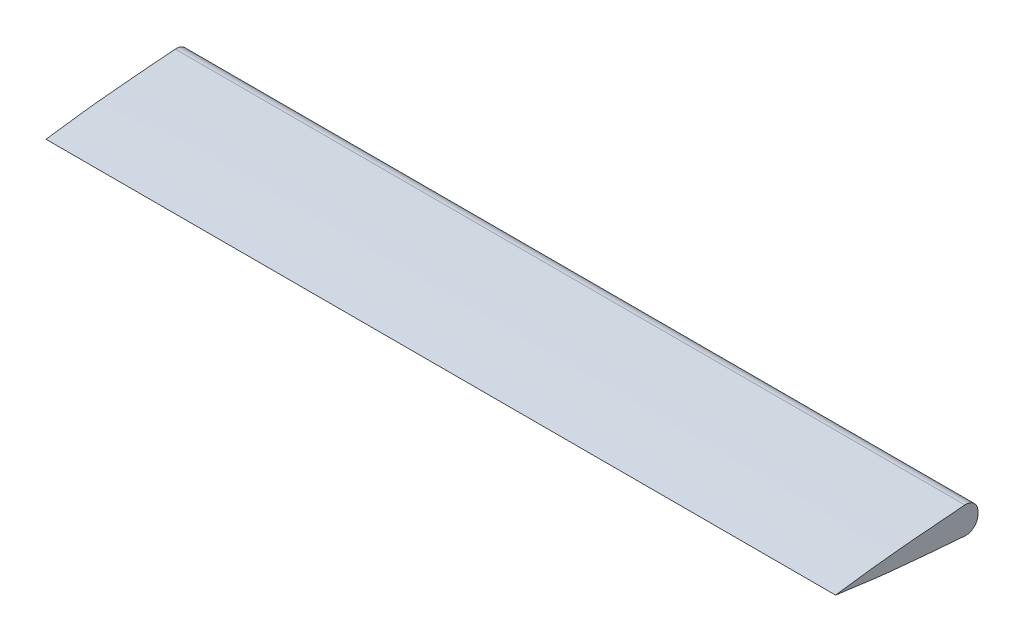
SolidWorks part; units mm, degrees
ref_plane "Front Plane" through (0, 0, 0) normal (0, 0, 1) x (1, 0, 0)
ref_plane "Top Plane" through (0, 0, 0) normal (0, 1, 0) x (1, 0, 0)
ref_plane "Right Plane" through (0, 0, 0) normal (1, 0, 0) x (0, 0, -1)
sketch "Sketch2" plane through (0, 0, 0) normal (1, 0, 0) x (0, 0, -1)
  line L0 (0, -5.4672) -> (0, 1.6028) construction
  line L1 (0, -2.2422) -> (0, -1.6224)
  arc A0 (0, -2.2422) -> (-3.2225, -5.234) centre (-3, -2.2422) cw
  arc A1 (0, -1.6224) -> (-3.2229, 1.3693) centre (-3, -1.6224) ccw
  spline S0 degree 3 poles (-335.5502, 4951.4956) (-455.5083, 24.7306) (-239.5385, 25.8639) (-23.962, -3.4159) (-18.4191, -3.9597) (-12.8738, -4.4648) (-8.2489, -4.8479) (-4.5477, -5.1359) (279.5391, -26.2331) (573.1452, 98.086) (1036.2925, 4820.0013) knots -2.586939 -2.586939 -2.586939 -2.586939 0.841688 0.871453 0.901217 0.930982 0.960746 0.975628 0.990511 5.528601 5.528601 5.528601 5.528601 only from (-35, -1.9292) to (0, -5.4672) construction
  spline S1 degree 3 poles (1148.2734, -4772.4312) (688.0924, -170.6311) (334.6046, 26.2987) (-4.9332, 1.2437) (-9.5594, 0.8791) (-15.1077, 0.4023) (-20.6523, -0.1153) (-24.3429, -0.5199) (-26.9188, -0.853) (-28.3881, -1.0486) (-30.5921, -1.3422) (-1684.8593, -221.6534) (-3338.3918, -441.8669) (-4991.1832, -661.9823) knots -5.408035 -5.408035 -5.408035 -5.408035 0.006595 0.021477 0.051242 0.081006 0.110771 0.140535 0.140535 0.152419 0.164303 0.176187 26.912663 26.912663 26.912663 26.912663 only from (0, 1.6028) to (-35, -1.9292) construction
  spline S2 degree 3 poles (-35, -1.9292) (-33.1602, -2.1756) (-29.4805, -2.6663) (-23.962, -3.4159) (-18.4191, -3.9597) (-12.8738, -4.4648) (-8.2489, -4.8479) (-5.0314, -5.0983) (-3.6642, -5.2011) (-3.2225, -5.234) knots 0.811924 0.811924 0.811924 0.811924 0.841688 0.871453 0.901217 0.930982 0.960746 0.975628 0.982731 0.982731 0.982731 0.982731
  spline S3 degree 3 poles (-3.2229, 1.3693) (-3.4845, 1.3498) (-5.597, 1.1914) (-9.5594, 0.8791) (-15.1077, 0.4023) (-20.6523, -0.1153) (-24.3429, -0.5199) (-26.9188, -0.853) (-28.3881, -1.0486) (-30.5921, -1.3422) (-32.796, -1.6357) (-34.2653, -1.8313) (-35, -1.9292) knots 0.017272 0.017272 0.017272 0.017272 0.021477 0.051242 0.081006 0.110771 0.140535 0.140535 0.152419 0.164303 0.176187 0.188071 0.188071 0.188071 0.188071
  dimension "D1" = 3
extrude "Boss-Extrude1" add sketch "Sketch2" along normal mid plane 190
ref_plane "Plane1" through (0, -1.9292, 0) normal (0, -1, 0) x (-1, 0, 0)
sketch "Sketch3" plane through (0, -1.9292, 0) normal (0, -1, 0) x (-1, 0, 0)
  line L0 (-95, 0) -> (95, 0) construction
  line L1 (-75, 0) -> (-63, 0)
  line L2 (-75, 0) -> (-75, -12)
  line L3 (-75, -12) -> (-63, -12)
  line L4 (-63, 0) -> (-63, -12)
  line L5 (75, 0) -> (97.5, 0) construction
  line L6 (63, 0) -> (75, 0)
  line L7 (63, 0) -> (63, -12)
  line L8 (63, -12) -> (75, -12)
  line L9 (75, 0) -> (75, -12)
  line L10 (95, -35) -> (95, -3.2225) construction
  line L11 (-95, -3.2225) -> (-95, -35) construction
  dimension "D1" = 12
  dimension "D2" = 12
  dimension "D3" = 12
  dimension "D4" = 12
  dimension "D5" = 20
  dimension "D6" = 20
extrude "Cut-Extrude1" cut sketch "Sketch3" along normal through all
sketch "Sketch4" plane through (-95, 0, 0) normal (-1, 0, 0) x (0, 0, 1)
  line L1 (0, -1.6224) -> (0, -2.2422)
  line L2 (0, -1.6224) -> (0, -2.2422)
  arc A2 (3.2229, 1.3693) -> (0, -1.6224) centre (3, -1.6224) ccw
  arc A3 (0, -2.2422) -> (3.2225, -5.234) centre (3, -2.2422) ccw
  arc A4 (3.2229, 1.3693) -> (0, -1.6224) centre (3, -1.6224) ccw
  arc A5 (0, -2.2422) -> (3.2225, -5.234) centre (3, -2.2422) ccw
  spline S2 degree 3 poles (3008.7348, -397.964) (2015.286, -265.6589) (1021.1024, -133.2559) (26.9188, -0.853) (24.3429, -0.5199) (20.6523, -0.1153) (15.1077, 0.4023) (9.5594, 0.8791) (-245.949, 21.0167) (-508.4621, -74.7572) (-795.8487, -2833.7019) knots -16.017597 -16.017597 -16.017597 -16.017597 0.052924 0.064808 0.064808 0.094573 0.124337 0.154101 0.183866 4.234112 4.234112 4.234112 4.234112 only from (35, -1.9292) to (3.2229, 1.3693)
  spline S3 degree 3 poles (-71.5909, -2906.952) (-657.6137, 144.6729) (-317.4172, -30.1897) (8.2489, -4.8479) (12.8738, -4.4648) (18.4191, -3.9597) (23.962, -3.4159) (205.7794, 21.2787) (387.3404, 24.3361) (368.8062, 2951.9217) knots -4.374254 -4.374254 -4.374254 -4.374254 0.819026 0.833908 0.863673 0.893437 0.923202 0.952966 3.835351 3.835351 3.835351 3.835351 only from (3.2225, -5.234) to (35, -1.9292)
  spline S4 degree 3 poles (35, -1.9292) (32.796, -1.6357) (29.8574, -1.2443) (26.9188, -0.853) (24.3429, -0.5199) (20.6523, -0.1153) (15.1077, 0.4023) (9.5594, 0.8791) (5.597, 1.1914) (3.4845, 1.3498) (3.2229, 1.3693) knots 0.017272 0.017272 0.017272 0.017272 0.052924 0.064808 0.064808 0.094573 0.124337 0.154101 0.183866 0.188071 0.188071 0.188071 0.188071
  spline S5 degree 3 poles (3.2225, -5.234) (3.6642, -5.2011) (5.0314, -5.0983) (8.2489, -4.8479) (12.8738, -4.4648) (18.4191, -3.9597) (23.962, -3.4159) (29.4805, -2.6663) (33.1602, -2.1756) (35, -1.9292) knots 0.811924 0.811924 0.811924 0.811924 0.819026 0.833908 0.863673 0.893437 0.923202 0.952966 0.982731 0.982731 0.982731 0.982731
  dimension "D1" = 0
extrude "Boss-Extrude2" add sketch "Sketch4" along normal blind 2
sketch "Sketch5" plane through (95, 0, 0) normal (1, 0, 0) x (0, 0, -1)
  line L1 (0, -2.2422) -> (0, -1.6224)
  line L2 (0, -2.2422) -> (0, -1.6224)
  arc A2 (-3.2225, -5.234) -> (0, -2.2422) centre (-3, -2.2422) ccw
  arc A3 (0, -1.6224) -> (-3.2229, 1.3693) centre (-3, -1.6224) ccw
  arc A4 (-3.2225, -5.234) -> (0, -2.2422) centre (-3, -2.2422) ccw
  arc A5 (0, -1.6224) -> (-3.2229, 1.3693) centre (-3, -1.6224) ccw
  spline S2 degree 3 poles (795.8716, -2833.9224) (508.476, -74.7622) (245.9557, 21.0172) (-9.5594, 0.8791) (-15.1077, 0.4023) (-20.6523, -0.1153) (-24.3429, -0.5199) (-26.9188, -0.853) (-1021.0987, -133.2554) (-2015.2786, -265.6579) (-3008.7237, -397.9625) knots -4.028876 -4.028876 -4.028876 -4.028876 0.021477 0.051242 0.081006 0.110771 0.140535 0.140535 0.152419 16.222881 16.222881 16.222881 16.222881 only from (-3.2229, 1.3693) to (-35, -1.9292)
  spline S3 degree 3 poles (-368.8056, 2952.0083) (-387.344, 24.3362) (-205.7811, 21.2789) (-23.962, -3.4159) (-18.4191, -3.9597) (-12.8738, -4.4648) (-8.2489, -4.8479) (317.4156, -30.1896) (657.6103, 144.6712) (71.5998, -2906.9056) knots -2.040725 -2.040725 -2.040725 -2.040725 0.841688 0.871453 0.901217 0.930982 0.960746 0.975628 6.168882 6.168882 6.168882 6.168882 only from (-35, -1.9292) to (-3.2225, -5.234)
  spline S4 degree 3 poles (-3.2229, 1.3693) (-3.4845, 1.3498) (-5.597, 1.1914) (-9.5594, 0.8791) (-15.1077, 0.4023) (-20.6523, -0.1153) (-24.3429, -0.5199) (-26.9188, -0.853) (-29.8574, -1.2443) (-32.796, -1.6357) (-35, -1.9292) knots 0.017272 0.017272 0.017272 0.017272 0.021477 0.051242 0.081006 0.110771 0.140535 0.140535 0.152419 0.188071 0.188071 0.188071 0.188071
  spline S5 degree 3 poles (-35, -1.9292) (-33.1602, -2.1756) (-29.4805, -2.6663) (-23.962, -3.4159) (-18.4191, -3.9597) (-12.8738, -4.4648) (-8.2489, -4.8479) (-5.0314, -5.0983) (-3.6642, -5.2011) (-3.2225, -5.234) knots 0.811924 0.811924 0.811924 0.811924 0.841688 0.871453 0.901217 0.930982 0.960746 0.975628 0.982731 0.982731 0.982731 0.982731
  dimension "D1" = 0
extrude "Boss-Extrude3" add sketch "Sketch5" along normal blind 2
